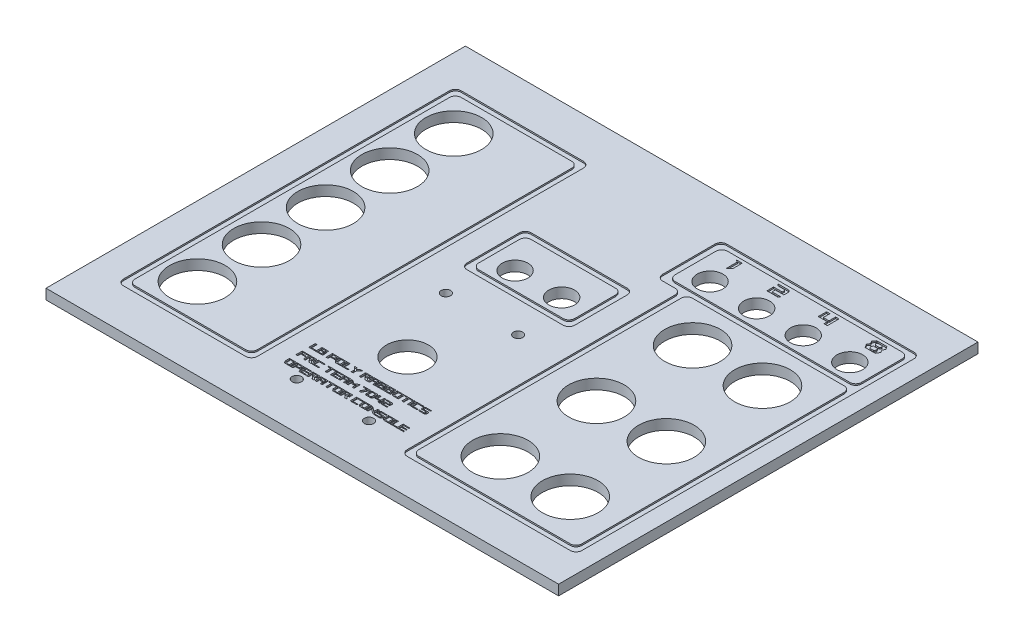
SolidWorks part; units mm, degrees
ref_plane "Front Plane" through (0, 0, 0) normal (0, 0, 1) x (1, 0, 0)
ref_plane "Top Plane" through (0, 0, 0) normal (0, 1, 0) x (1, 0, 0)
ref_plane "Right Plane" through (0, 0, 0) normal (1, 0, 0) x (0, 0, -1)
sketch "Sketch1" plane through (0, 0, 0) normal (0, 1, 0) x (1, 0, 0)
  line L1 (139.7, 114.3) -> (-139.7, 114.3)
  line L2 (139.7, 114.3) -> (139.7, -114.3)
  line L3 (139.7, -114.3) -> (-139.7, -114.3)
  line L4 (-139.7, 114.3) -> (-139.7, -114.3)
  line L5 (0, -114.3) -> (0, 114.3) construction
  line L6 (139.7, 0) -> (-139.7, 0) construction
  point P0 (0, 0)
  dimension "D1" = 279.4
  dimension "D2" = 228.6
extrude "Boss-Extrude1" add sketch "Sketch1" along normal blind 5.5562
sketch "Sketch2" plane through (0, 5.5562, 0) normal (0, 1, 0) x (1, 0, 0)
  line L1 (-139.7, 114.3) -> (-139.7, -114.3) construction
  circle A0 centre (-101.6, 69.85) radius 15.1606
  circle A3 centre (-101.6, 34.925) radius 15.1606
  circle A4 centre (-101.6, 0) radius 15.1606
  circle A5 centre (-101.6, -34.925) radius 15.1606
  circle A6 centre (-101.6, -69.85) radius 15.1606
  point P15 (-139.7, 0)
  dimension "D1" = 5
  dimension "D2" = 30.3213
  dimension "D3" = 34.925
  dimension "D4" = 38.1
extrude "Cut-Extrude1" cut sketch "Sketch2" against normal through all
sketch "Sketch3" plane through (0, 5.5562, 0) normal (0, 1, 0) x (1, 0, 0)
  line L0 (-101.6, 69.85) -> (38.1, 69.85) construction
  line L1 (-101.6, 34.925) -> (63.5, 34.925) construction
  line L2 (139.7, -114.3) -> (139.7, 114.3) construction
  line L3 (101.6, 34.925) -> (101.6, -17.4625) construction
  line L4 (-101.6, -85.0106) -> (63.5, -85.0106) construction
  circle A0 centre (38.1, 69.85) radius 7.0247
  circle A1 centre (63.5, 69.85) radius 7.0247
  circle A2 centre (88.9, 69.85) radius 7.0247
  circle A3 centre (114.3, 69.85) radius 7.0247
  circle A6 centre (63.5, 34.925) radius 15.1606
  circle A7 centre (101.6, 34.925) radius 15.1606
  circle A8 centre (-101.6, -69.85) radius 15.1606 construction
  circle A10 centre (101.6, -17.4625) radius 15.1606
  circle A11 centre (63.5, -17.4625) radius 15.1606
  circle A12 centre (101.6, -69.85) radius 15.1606
  circle A13 centre (63.5, -69.85) radius 15.1606
  dimension "D1" = 14.0494
  dimension "D5" = 38.1
  dimension "D6" = 30.3213
  dimension "D3" = 12.7
  dimension "D4" = 25.4
  dimension "D7" = 38.1
  dimension "D2" = 4
  dimension "D8" = 3
extrude "Cut-Extrude2" cut sketch "Sketch3" against normal through all
sketch "Sketch4" plane through (0, 5.5562, 0) normal (0, 1, 0) x (1, 0, 0)
  line L0 (-49.9269, -92.075) -> (-122.9519, -92.075)
  line L1 (-53.1019, -88.9) -> (-119.7769, -88.9)
  line L3 (-53.1019, 88.9) -> (-119.7769, 88.9)
  line L4 (-119.7769, -88.9) -> (-119.7769, 88.9)
  line L5 (-86.4394, 88.9) -> (-86.4394, -88.9) construction
  line L6 (-53.1019, 0) -> (-119.7769, 0) construction
  line L7 (-122.9519, -92.075) -> (-122.9519, 92.075)
  line L8 (-49.9269, 92.075) -> (-122.9519, 92.075)
  line L9 (-49.9269, -92.075) -> (-49.9269, 92.075)
  line L10 (38.1, 57.15) -> (127, -92.075) construction
  line L12 (38.1, 57.15) -> (38.1, -92.075)
  line L13 (38.1, -92.075) -> (127, -92.075)
  line L14 (127, 57.15) -> (127, -92.075)
  line L15 (63.5, -17.4625) -> (101.6, -17.4625) construction
  line L17 (130.175, 60.325) -> (130.175, -95.25)
  line L18 (34.925, -95.25) -> (130.175, -95.25)
  line L19 (34.925, 57.15) -> (34.925, -95.25)
  line L22 (127, 57.15) -> (38.1, 57.15)
  line L24 (127, 88.9) -> (127, 60.325)
  line L26 (-53.1019, 88.9) -> (-53.1019, -88.9)
  line L27 (-49.9269, -92.075) -> (-49.9269, 92.075) construction
  line L28 (-53.1019, -88.9) -> (-53.1019, 88.9) construction
  line L30 (34.925, 60.325) -> (34.925, -95.25) construction
  line L31 (34.925, 60.325) -> (130.175, 60.325) construction
  line L33 (34.925, 57.15) -> (21.7795, 57.15)
  line L34 (38.1, 57.15) -> (127, 57.15) construction
  line L35 (21.7795, 57.15) -> (21.7795, 92.075)
  line L36 (21.7795, 92.075) -> (130.175, 92.075)
  line L37 (127, 88.9) -> (25.4, 88.9)
  line L38 (25.4, 88.9) -> (25.4, 60.325)
  line L39 (25.4, 60.325) -> (127, 60.325)
  line L40 (130.175, 60.325) -> (130.175, 92.075)
  circle A0 centre (-101.6, 0) radius 15.1606 construction
  circle A1 centre (63.5, -17.4625) radius 15.1606 construction
  circle A2 centre (63.5, 69.85) radius 7.0247 construction
  circle A4 centre (38.1, 69.85) radius 7.0247 construction
  circle A5 centre (114.3, 69.85) radius 7.0247 construction
  point P0 (-86.4394, 0)
  point P20 (82.3396, -17.4625)
  point P23 (82.55, -17.4625)
  point P29 (82.55, -17.4625)
  dimension "D9" = 12.7
  dimension "D7" = 12.7
  dimension "D1" = 33.3375
  dimension "D2" = 88.9
  dimension "D4" = 12.7
  dimension "D5" = 3.175
  dimension "D6" = 88.9
  dimension "D8" = 3.6205
  dimension "D11" = 3.175
  dimension "D12" = 3.175
  dimension "D3" = 3.175
extrude "Cut-Extrude3" cut sketch "Sketch4" against normal blind 0.7937
fillet "Fillet1" radius 3.175 22 edges at (130.175, 5.1594, 95.25) (127, 5.1594, 92.075) (34.925, 5.1594, 95.25) (38.1, 5.1594, 92.075) (-119.7769, 5.1594, 88.9) (-122.9519, 5.1594, 92.075) (-49.9269, 5.1594, 92.075) (-53.1019, 5.1594, 88.9) (38.1, 5.1594, -57.15) (127, 5.1594, -57.15) (34.925, 5.1594, -57.15) (127, 5.1594, -60.325) (130.175, 5.1594, -92.075) (127, 5.1594, -88.9) (21.7795, 5.1594, -57.15) (25.4, 5.1594, -60.325) (21.7795, 5.1594, -92.075) (25.4, 5.1594, -88.9) (-49.9269, 5.1594, -92.075) (-53.1019, 5.1594, -88.9) (-122.9519, 5.1594, -92.075) (-119.7769, 5.1594, -88.9)
sketch "Sketch5" plane through (0, 5.5562, 0) normal (0, 1, 0) x (1, 0, 0)
  line L0 (-40.4019, -70.556) -> (27.4392, -70.556) construction
  line L1 (-49.9269, -88.9) -> (-49.9269, 88.9) construction
  text T0 "LB Poly Rabbotics\r\nFRC Team 7042\r\nOperator Console" font "ROG Fonts" height 3.5
  dimension "D1" = 9.525
extrude "Cut-Extrude4" cut sketch "Sketch5" against normal blind 0.7937
sketch "Sketch6" plane through (0, 5.5562, 0) normal (0, 1, 0) x (1, 0, 0)
  line L0 (32.0219, 80.9625) -> (119.1467, 80.9625) construction
  line L1 (123.825, 88.9) -> (28.575, 88.9) construction
  text T0 " 1       2       4       8" font "ROG Fonts" height 6.35
  dimension "D1" = 7.9375
extrude "Cut-Extrude5" cut sketch "Sketch6" against normal blind 0.7937
sketch "Sketch7" plane through (0, 5.5562, 0) normal (0, 1, 0) x (1, 0, 0)
  line L0 (-33.6947, 44.0928) -> (18.6928, 44.0928)
  line L1 (-30.5197, 40.9178) -> (15.5178, 40.9178)
  line L2 (-33.6947, 37.7428) -> (-33.6947, 15.5178)
  line L3 (-30.5197, 12.3428) -> (15.5178, 12.3428)
  line L4 (18.6928, 37.7428) -> (18.6928, 15.5178)
  line L5 (-7.5009, 12.3428) -> (-7.5009, 40.9178) construction
  line L6 (-33.6947, 26.6303) -> (18.6928, 26.6303) construction
  line L7 (21.8678, 40.9178) -> (21.8678, 12.3428)
  line L8 (-33.6947, 9.1678) -> (18.6928, 9.1678)
  line L9 (-36.8697, 40.9178) -> (-36.8697, 12.3428)
  line L10 (-36.8697, 31.8817) -> (-49.9269, 31.8817) construction
  line L11 (-49.9269, -88.9) -> (-49.9269, 88.9) construction
  line L12 (21.8678, 31.8817) -> (34.925, 31.8817) construction
  line L13 (34.925, 53.975) -> (34.925, -92.075) construction
  line L14 (-36.8697, 9.1678) -> (21.8678, 9.1678) construction
  line L15 (-36.8697, 44.0928) -> (-36.8697, 9.1678) construction
  line L16 (-33.6947, 40.9178) -> (-33.6947, 12.3428) construction
  line L17 (-33.6947, 12.3428) -> (18.6928, 12.3428) construction
  line L18 (21.8678, 44.0928) -> (21.8678, 9.1678) construction
  line L19 (18.6928, 40.9178) -> (18.6928, 12.3428) construction
  line L20 (-36.8697, 44.0928) -> (21.8678, 44.0928) construction
  line L21 (-33.6947, 40.9178) -> (18.6928, 40.9178) construction
  line L22 (24.9545, 57.15) -> (24.9545, 44.0928) construction
  arc A0 (-33.6947, 9.1678) -> (-36.8697, 12.3428) centre (-33.6947, 12.3428) cw
  arc A1 (-33.6947, 15.5178) -> (-30.5197, 12.3428) centre (-30.5197, 15.5178) ccw
  arc A2 (21.8678, 12.3428) -> (18.6928, 9.1678) centre (18.6928, 12.3428) cw
  arc A3 (15.5178, 12.3428) -> (18.6928, 15.5178) centre (15.5178, 15.5178) ccw
  arc A4 (18.6928, 44.0928) -> (21.8678, 40.9178) centre (18.6928, 40.9178) cw
  arc A5 (15.5178, 40.9178) -> (18.6928, 37.7428) centre (15.5178, 37.7428) cw
  arc A6 (-33.6947, 44.0928) -> (-36.8697, 40.9178) centre (-33.6947, 40.9178) ccw
  arc A7 (-30.5197, 40.9178) -> (-33.6947, 37.7428) centre (-30.5197, 37.7428) ccw
  point P0 (-7.5009, 26.6303)
  dimension "D2" = 3.175
  dimension "D1" = 3.175
  dimension "D3" = 28.575
  dimension "D4" = 26.1937
extrude "Cut-Extrude6" cut sketch "Sketch7" against normal blind 0.7937
sketch "Sketch8" plane through (0, 5.5562, 0) normal (0, 1, 0) x (1, 0, 0)
  line L0 (-7.5009, 12.3428) -> (-7.5009, 27.5264) construction
  line L1 (-30.5197, 12.3428) -> (15.5178, 12.3428) construction
  line L2 (-30.5197, 12.3428) -> (15.5178, 12.3428) construction
  circle A0 centre (-20.2009, 21.8678) radius 7.0247
  circle A1 centre (5.1991, 21.8678) radius 7.0247
  dimension "D1" = 14.0494
  dimension "D2" = 25.4
  dimension "D3" = 9.525
extrude "Cut-Extrude7" cut sketch "Sketch8" against normal through all
sketch "Sketch9" plane through (0, 5.5562, 0) normal (0, 1, 0) x (1, 0, 0)
  line L0 (139.7, -114.3) -> (139.7, 114.3) construction
  line L1 (-139.7, -114.3) -> (139.7, -114.3) construction
  circle A0 centre (-8.7254, -48.26) radius 11.43
  circle A1 centre (10.9596, -7.62) radius 2.54
  circle A2 centre (10.9596, -88.9) radius 2.54
  circle A3 centre (-28.4104, -7.62) radius 2.54
  circle A4 centre (-28.4104, -88.9) radius 2.54
  point P2 (-6.35, -30.8805)
  point P3 (-6.35, -30.8805)
  point P4 (-6.35, -32.8303)
  point P5 (13.335, 9.7595)
  point P15 (0, 0)
  point P16 (0, 0)
  point P17 (-27.9772, 7.285)
  point P18 (0, 0)
  point P19 (0, 0)
  point P20 (0, 0)
  point P21 (-8.6285, -32.2414)
  point P22 (0, 0)
  point P23 (-4.9357, -39.365)
  point P24 (-8.9187, -29.1277)
  point P25 (-7.8331, -35.5028)
  point P26 (-8.7254, -32.4485)
  point P29 (-28.4104, -89.6444)
  point P30 (-28.4104, -88.3486)
  dimension "D1" = 22.86
  dimension "D6" = 5.08
  dimension "D7" = 5.08
  dimension "D9" = 5.08
  dimension "D10" = 5.08
  dimension "D2" = 39.37
  dimension "D3" = 19.685
  dimension "D4" = 81.28
  dimension "D5" = 40.64
  dimension "D8" = 148.4254
  dimension "D11" = 66.04
extrude "Cut-Extrude8" cut sketch "Sketch9" against normal through all
